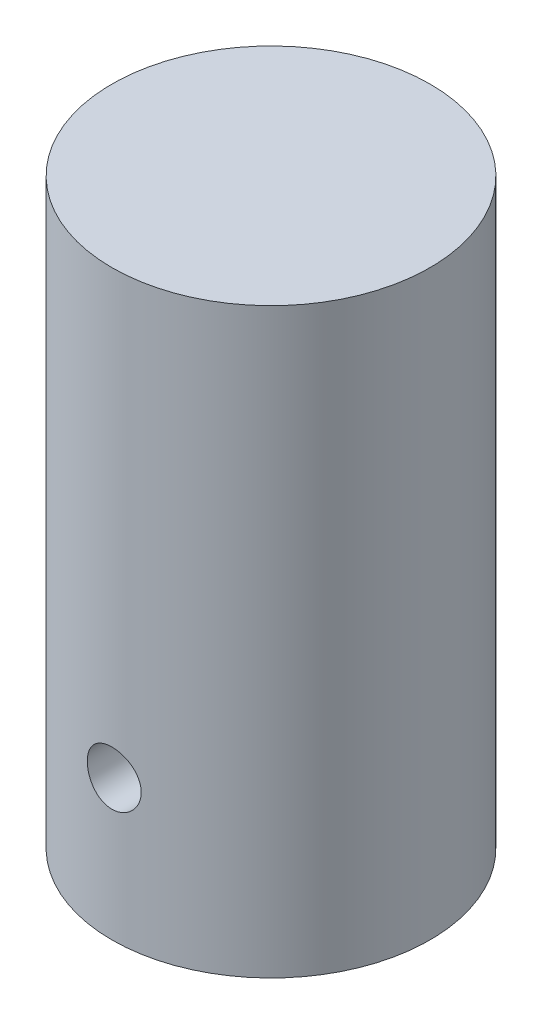
SolidWorks part; units mm, degrees
ref_plane "Front Plane" through (0, 0, 0) normal (0, 0, 1) x (1, 0, 0)
ref_plane "Top Plane" through (0, 0, 0) normal (0, 1, 0) x (1, 0, 0)
ref_plane "Right Plane" through (0, 0, 0) normal (1, 0, 0) x (0, 0, -1)
sketch "Sketch1" plane through (0, 0, 0) normal (0, 1, 0) x (1, 0, 0)
  circle A0 centre (0, 0) radius 37.465
  dimension "D1" = 74.93
extrude "Boss-Extrude1" add sketch "Sketch1" along normal blind 137.16
ref_plane "Plane1" through (0, 0, 37.465) normal (0, 0, 1) x (1, 0, 0)
sketch "Sketch3" plane through (0, 0, 37.465) normal (0, 0, 1) x (1, 0, 0)
  line L0 (0, 0) -> (0, 33.02) construction
  circle A0 centre (0, 33.02) radius 6.35
  dimension "D2" = 12.7
  dimension "D1" = 33.02
sketch "Sketch4" plane through (0, 0, 0) normal (0, -1, 0) x (1, 0, 0)
  circle A0 centre (0, 0) radius 6.35
  dimension "D1" = 12.7
extrude "Cut-Extrude2" cut sketch "Sketch4" against normal blind 19.05
extrude "Cut-Extrude3" cut sketch "Sketch3" against normal blind 19.05
